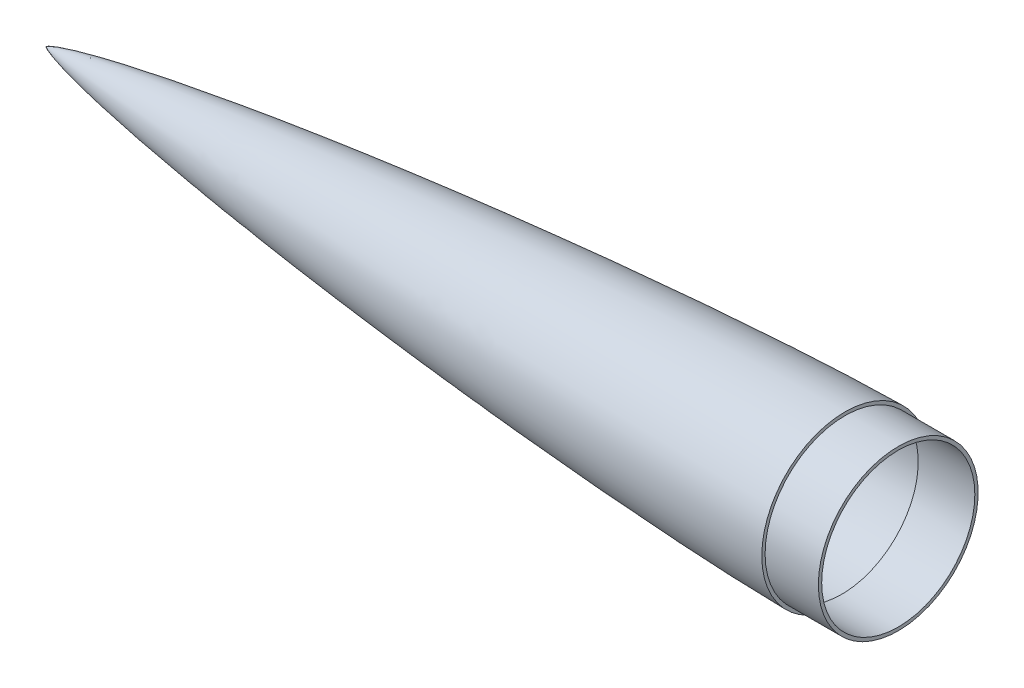
SolidWorks part; units mm, degrees
ref_plane "Front Plane" through (0, 0, 0) normal (0, 0, 1) x (1, 0, 0)
ref_plane "Top Plane" through (0, 0, 0) normal (0, 1, 0) x (1, 0, 0)
ref_plane "Right Plane" through (0, 0, 0) normal (1, 0, 0) x (0, 0, -1)
ref_axis "Axis1" through (-22.86, 0, 0) along (1, 0, 0)
sketch "Sketch1" plane through (0, 0, 0) normal (0, 0, 1) x (1, 0, 0)
  line L0 (406.4, 0) -> (0, 0)
  line L1 (43.6423, 0) -> (-43.6423, 0) construction
  line L4 (381, 38.1) -> (406.4, 38.1)
  line L5 (406.4, 38.1) -> (406.4, 0)
  line L7 (381, 38.1) -> (381, 39.6748)
  spline S0 degree 4 poles (0, 0) (0.003, 0.0074) (0.0105, 0.0213) (0.0311, 0.0458) (0.0656, 0.0788) (0.1085, 0.1142) (0.1696, 0.1593) (0.2429, 0.2084) (0.3536, 0.2764) (0.5216, 0.37) (0.7712, 0.4962) (1.1804, 0.6832) (1.8685, 0.9654) (3.0994, 1.4129) (5.367, 2.1346) (9.5884, 3.2967) (16.8729, 5.0187) (29.3641, 7.5637) (46.5722, 10.5749) (67.5031, 13.8025) (90.9083, 17.0332) (114.35, 19.9843) (137.8197, 22.7032) (161.3118, 25.2203) (184.8229, 27.5534) (208.3505, 29.7136) (231.8929, 31.7062) (255.4488, 33.5316) (279.0174, 35.1854) (302.5981, 36.6571) (323.2415, 37.7687) (340.9432, 38.5739) (355.1716, 39.1048) (364.7115, 39.3936) (372.5129, 39.5736) (377.3625, 39.648) (379.7875, 39.6717) (381, 39.6748) knots 0 0 0 0 0 0.000083 0.000166 0.000331 0.000497 0.000662 0.000957 0.001251 0.00185 0.002667 0.00387 0.005939 0.009599 0.016314 0.028666 0.051563 0.087599 0.14916 0.21072 0.272281 0.333842 0.395403 0.456964 0.518524 0.580085 0.641646 0.703207 0.764768 0.826328 0.887889 0.91867 0.94945 0.974725 0.987363 1 1 1 1 1 construction
  spline S1 degree 4 poles (0, 0) (0.003, 0.0074) (0.0105, 0.0213) (0.0311, 0.0458) (0.0656, 0.0788) (0.1085, 0.1142) (0.1696, 0.1593) (0.2429, 0.2084) (0.3536, 0.2764) (0.5216, 0.37) (0.7712, 0.4962) (1.1804, 0.6832) (1.8685, 0.9654) (3.0994, 1.4129) (5.367, 2.1346) (9.5884, 3.2967) (16.8729, 5.0187) (29.3641, 7.5637) (46.5722, 10.5749) (67.5031, 13.8025) (90.9083, 17.0332) (114.35, 19.9843) (137.8197, 22.7032) (161.3118, 25.2203) (184.8229, 27.5534) (208.3505, 29.7136) (231.8929, 31.7062) (255.4488, 33.5316) (279.0174, 35.1854) (302.5981, 36.6571) (323.2415, 37.7687) (340.9432, 38.5739) (355.1716, 39.1048) (364.7115, 39.3936) (372.5129, 39.5736) (377.3625, 39.648) (379.7875, 39.6717) (381, 39.6748) knots 0 0 0 0 0 0.000083 0.000166 0.000331 0.000497 0.000662 0.000957 0.001251 0.00185 0.002667 0.00387 0.005939 0.009599 0.016314 0.028666 0.051563 0.087599 0.14916 0.21072 0.272281 0.333842 0.395403 0.456964 0.518524 0.580085 0.641646 0.703207 0.764768 0.826328 0.887889 0.91867 0.94945 0.974725 0.987363 1 1 1 1 1
  point P2 (0, 0)
  point P7 (0, 0)
  point P8 (21.556, 19.6917)
  point P10 (-27.8261, 110.6963)
  point P11 (0, 0)
  point P12 (459.192, 4.3636)
  point P13 (0, 0)
  point P14 (0, 0)
  point P15 (443.6666, 0)
  point P16 (0, 0)
  point P17 (0, 0)
  point P18 (-52.8105, 58.7706)
  point P19 (-64.735, 53.7023)
  point P20 (-67.624, 134.2212)
  dimension "D2" = 38.1
  dimension "D4" = 25.4
  dimension "D1" = 39.6748
  dimension "D3" = 381
revolve "Revolve1" add sketch "Sketch1" angle 360 about axis through (-22.86, 0, 0) along (1, 0, 0) region at (250.206, 15.5728, 0)
shell "Shell3" thickness 1.5875 removed face at (406.4, 0, 38.1)
equation "\"D_o\"= 3.124in"
equation "\"D_i\"= 3in"
equation "\"D_c\"= 2.88in"
equation "\"L\"= 15"
equation "\"L_s\"= 1in"
equation "\"D2@Sketch1\"=\"D_i\"/2"
equation "\"D4@Sketch1\"=\"L_s\""
equation "\"D1@Sketch1\"=\"D_o\"/2"
equation "\"D3@Sketch1\"=\"L\""
equation "\"D1@Shell3\"=1/16"
